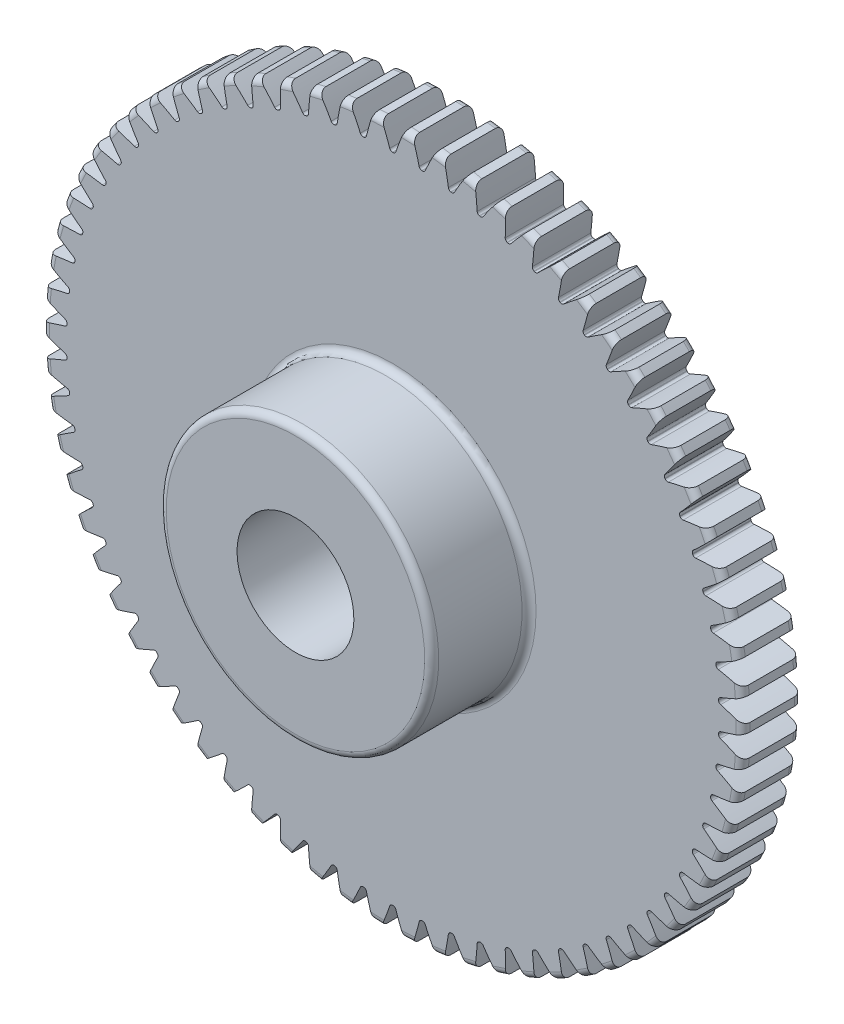
SolidWorks part; units mm, degrees
ref_plane "Front Plane" through (0, 0, 0) normal (0, 0, 1) x (1, 0, 0)
ref_plane "Top Plane" through (0, 0, 0) normal (0, 1, 0) x (1, 0, 0)
ref_plane "Right Plane" through (0, 0, 0) normal (1, 0, 0) x (0, 0, -1)
sketch "Sketch1" plane through (0, 0, 0) normal (0, 0, 1) x (1, 0, 0)
  line L0 (-889, 0) -> (889, 0) construction
  circle A0 centre (0, 0) radius 18 construction
  circle A1 centre (0, 0) radius 17.5 construction
  circle A2 centre (0, 0) radius 16.75 construction
  circle A3 centre (0, 0) radius 7 construction
  circle A4 centre (0, 0) radius 3 construction
  dimension "D2" = 0.5
  dimension "D3" = 1.25
  dimension "D1" = 1.25
sketch "Sketch2" plane through (0, 0, 0) normal (1, 0, 0) x (0, 0, -1)
  line L0 (0, 0) -> (-3, 0) construction
  line L1 (-3, 0) -> (-8, 0) construction
  dimension "Overall Width" = 8
  dimension "Face Width" = 3
sketch "Sketch4" plane through (0, 0, 0) normal (1, 0, 0) x (0, 0, -1)
  line L0 (-8, 3) -> (-8, 7)
  line L1 (-8, 7) -> (-3, 7)
  line L2 (-3, 7) -> (-3, 18)
  line L3 (-3, 18) -> (0, 18)
  line L4 (0, 18) -> (0, 3)
  line L5 (-3, 7) -> (-3, 0) construction
  line L6 (0, 18) -> (0, -18) construction
  line L7 (-3, 7) -> (0, 7) construction
  line L12 (-8, 3) -> (0, 3)
revolve "Revolve1" add sketch "Sketch4" angle 360 about L1
fillet "Fillet2" radius 0.36 4 edges at (0, 7, 8) (0, 7, 3) (0, 18, 3) (0, 18, 0)
sketch "Sketch7" plane through (0, 0, 3) normal (0, 0, 1) x (1, 0, 0)
  line L0 (0, 0) -> (0, 18) construction
  line L1 (0.3927, 17.4956) -> (0.5855, 17.9905) construction
  line L3 (0.8076, 17.9819) -> (0.7851, 17.4824) construction
  line L4 (0.7851, 17.4824) -> (0.7515, 16.7331) construction
  line L5 (0, 0) -> (0.7515, 16.7331) construction
  line L6 (0.3927, 17.4956) -> (0, 0) construction
  line L7 (0.3927, 17.4956) -> (0.4039, 17.9955) construction
  line L8 (0.3927, 17.4956) -> (0, 0) construction
  circle A0 centre (0, 0) radius 18 construction
  arc A1 (-0.0141, 16.75) -> (0.0141, 16.75) centre (0, 0) cw
  circle A2 centre (0, 0) radius 16.75 construction
  arc A3 (-0.3927, 17.4956) -> (0.3927, 17.4956) centre (0, 0) cw construction
  circle A4 centre (0, 0) radius 17.5 construction
  arc A5 (1.0209, 17.971) -> (0.5941, 17.9902) centre (0, 0) ccw construction
  arc A6 (0.3927, 17.4956) -> (1.1772, 17.4604) centre (0, 0) cw construction
  arc A7 (-0.5941, 17.9902) -> (0.5941, 17.9902) centre (0, 0) cw
  arc A8 (0.156, 16.8511) -> (0.5941, 17.9902) centre (16.6988, 11.1428) cw
  arc A9 (-0.156, 16.8511) -> (-0.5941, 17.9902) centre (-16.6988, 11.1428) ccw
  arc A10 (-0.0141, 16.75) -> (-0.156, 16.8511) centre (-0.0142, 16.9) cw
  arc A11 (0.0141, 16.75) -> (0.156, 16.8511) centre (0.0142, 16.9) ccw
  point P26 (-0.1213, 16.7496)
  point P29 (0.1213, 16.7496)
  dimension "D4" = 0.15
  dimension "D5" = 17.5
  dimension "D3" = 20
  dimension "D1" = 1.5708
  dimension "D2" = 0.7854
extrude "Cut-Extrude2" cut sketch "Sketch7" against normal through all
pattern_circular "CirPattern1" count 70 over 360 about axis through (0, 0, 8) along (0, 0, -1) of "Cut-Extrude2"
equation "\"D1@Sketch1\"=2.5*(\"Pitch Dia.@Sketch1\"/\"Number of Teeth@Sketch1\")"
equation "\"D1@CirPattern1\"=\"Number of Teeth@Sketch1\""
equation "\"D1@Fillet2\"=\"OD@Sketch1\"*.01"
equation "\"D1@Sketch7\"=3.14159*(\"Pitch Dia.@Sketch1\"/\"Number of Teeth@Sketch1\")"
equation "\"D2@Sketch7\"=\"D1@Sketch7\"/2"
equation "\"D4@Sketch7\"=\"D1@Sketch7\"*.0955"
equation "\"D5@Sketch7\"=\"Pitch Dia.@Sketch1\"/2"
